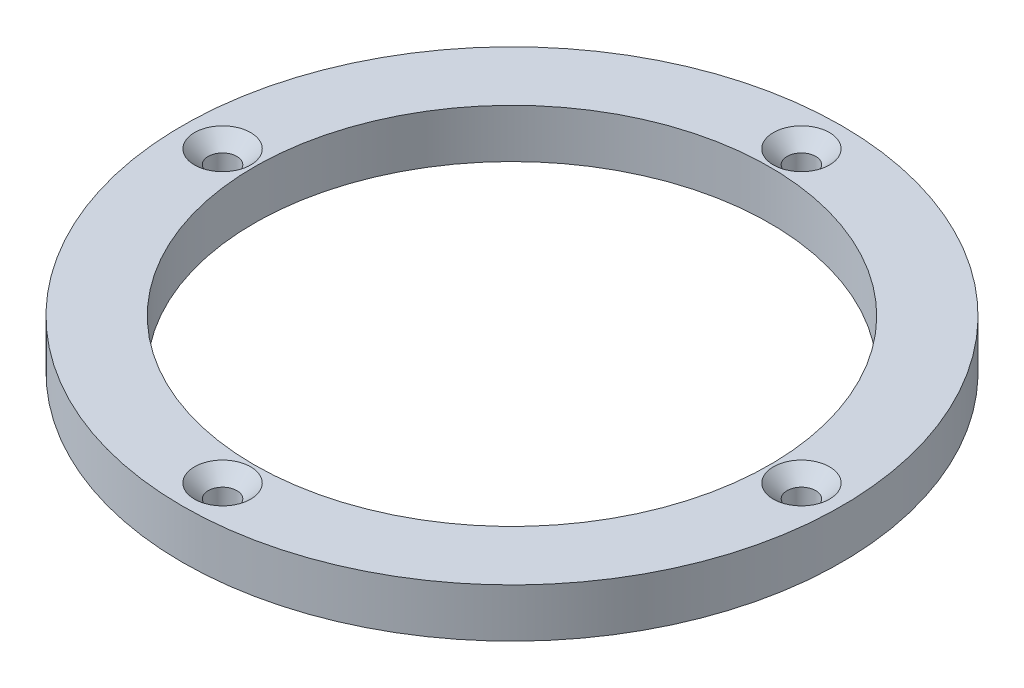
SolidWorks part; units mm, degrees
material "6061 合金"
ref_plane "前视基准面" through (0, 0, 0) normal (0, 0, 1) x (1, 0, 0)
ref_plane "上视基准面" through (0, 0, 0) normal (0, 1, 0) x (1, 0, 0)
ref_plane "右视基准面" through (0, 0, 0) normal (1, 0, 0) x (0, 0, -1)
other "Configuration Table"
sketch "草图1" plane through (0, 0, 0) normal (0, 1, 0) x (1, 0, 0)
  circle A0 centre (0, 0) radius 45
  circle A1 centre (0, 0) radius 57.5
  circle A2 centre (0, 0) radius 50.5 construction
  circle A3 centre (0, 50.5) radius 2.5
  circle A4 centre (50.5, 0) radius 2.5
  circle A5 centre (0, -50.5) radius 2.5
  circle A6 centre (-50.5, 0) radius 2.5
  dimension "D1" = 90
  dimension "D2" = 115
  dimension "D3" = 101
  dimension "D4" = 5
  dimension "D5" = 4
extrude "凸台-拉伸1" add sketch "草图1" against normal blind 8.5
ref_axis "基准轴1" through (0, -8.5, -50.5) along (0, 1, 0)
ref_plane "基准面1" through (0, 0, -50.5) normal (0, 0, 1) x (1, 0, 0)
sketch "草图2" plane through (0, 0, -50.5) normal (0, 0, 1) x (1, 0, 0)
  line L0 (0, 0) -> (4.9, 0)
  line L1 (57.5, 0) -> (-57.5, 0) construction
  line L2 (4.9, 0) -> (1.6, -3.3)
  line L3 (1.6, -3.3) -> (0, -3.3)
  line L4 (0, -8.5) -> (0, 0) construction
  line L5 (0, -3.3) -> (0, 0)
  point P5 (0, -3.3)
  dimension "D1" = 4.9
  dimension "D2" = 45
  dimension "D3" = 3.3
revolve "切除-旋转1" cut sketch "草图2" angle 360 about L5
pattern_circular "阵列(圆周)1" count 4 over 360 about axis through (0, -8.5, 0) along (0, 1, 0) of "切除-旋转1"
